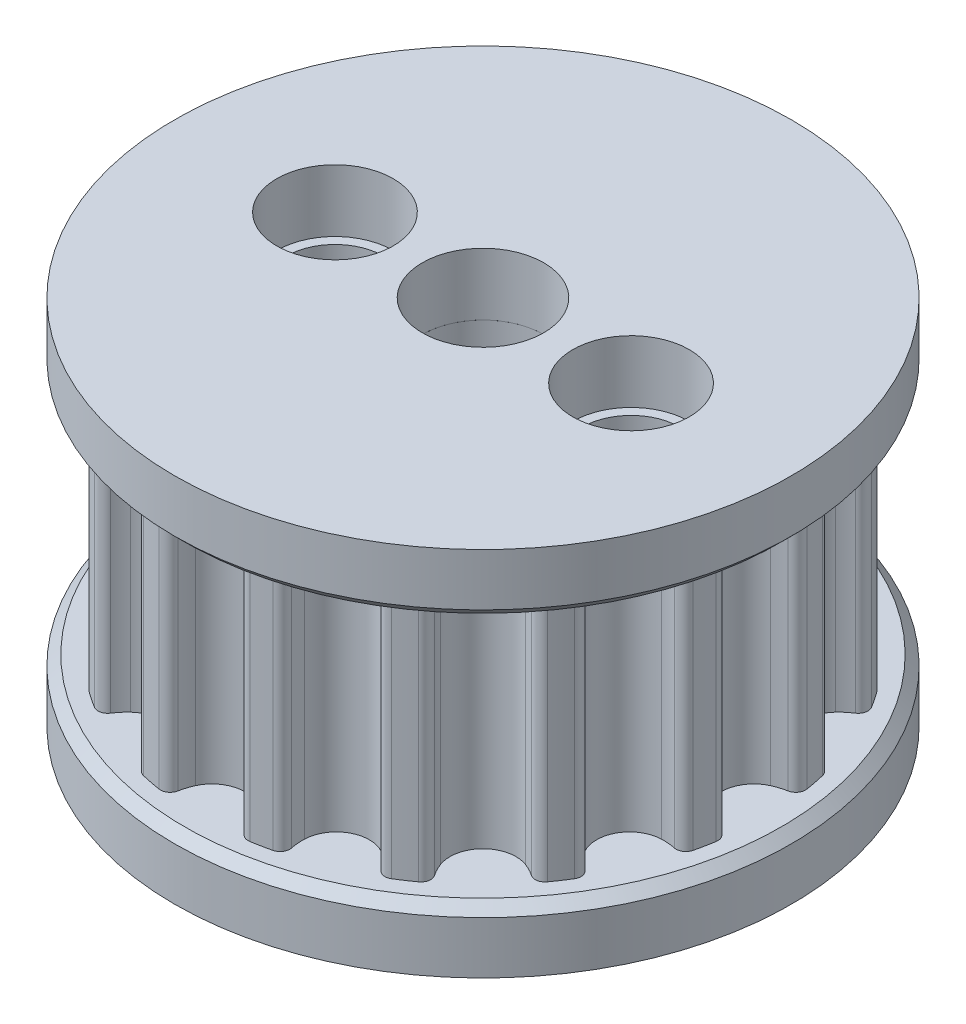
SolidWorks part; units mm, degrees
material "Alum Plate"
ref_plane "Front Plane" through (0, 0, 0) normal (0, 0, 1) x (1, 0, 0)
ref_plane "Top Plane" through (0, 0, 0) normal (0, 1, 0) x (1, 0, 0)
ref_plane "Right Plane" through (0, 0, 0) normal (1, 0, 0) x (0, 0, -1)
other "Bounding Box"
ref_plane "Default Plane" through (-8.9266, -12.7485, 0) normal (-0.1736, 0.9848, 0) x (0.9848, 0.1736, 0)
sketch "Sketch1" plane through (0, 0, 0) normal (0, 1, 0) x (1, 0, 0)
  line L0 (0, -7.8245) -> (0, 0) construction
  circle A0 centre (0, 0) radius 1.5625
  arc B0 (-1.8508, -6.777) -> (-1.6633, -7.0715) centre (-1.6061, -6.8282) ccw
  arc B1 (-1.6633, -7.0715) -> (-1.1695, -7.1697) centre (0, 0) ccw
  arc B2 (-1.1695, -7.1697) -> (-0.8836, -6.9694) centre (-1.1292, -6.923) ccw
  arc B3 (-0.7739, -6.6229) -> (-0.8836, -6.9694) centre (0.61, -7.2516) ccw
  arc B4 (0.7739, -6.6229) -> (-0.7739, -6.6229) centre (0, -6.9745) ccw
  arc B5 (0.8836, -6.9694) -> (0.7739, -6.6229) centre (-0.61, -7.2516) ccw
  arc B6 (0.8836, -6.9694) -> (1.1695, -7.1697) centre (1.1292, -6.923) ccw
  arc B7 (1.1695, -7.1697) -> (1.6633, -7.0715) centre (0, 0) ccw
  arc B8 (1.6633, -7.0715) -> (1.8508, -6.777) centre (1.6061, -6.8282) ccw
  arc B9 (1.8195, -6.4149) -> (1.8508, -6.777) centre (3.3386, -6.4662) ccw
  arc B10 (3.2495, -5.8226) -> (1.8195, -6.4149) centre (2.669, -6.4436) ccw
  arc B11 (3.4834, -6.1008) -> (3.2495, -5.8226) centre (2.2115, -6.9331) ccw
  arc B12 (3.4834, -6.1008) -> (3.8242, -6.1764) centre (3.6926, -5.9639) ccw
  arc B13 (3.8242, -6.1764) -> (4.2428, -5.8967) centre (0, 0) ccw
  arc B14 (4.2428, -5.8967) -> (4.3033, -5.5529) centre (4.0968, -5.6938) ccw
  arc B15 (4.1359, -5.2303) -> (4.3033, -5.5529) centre (5.559, -4.6963) ccw
  arc B16 (5.2303, -4.1359) -> (4.1359, -5.2303) centre (4.9317, -4.9317) ccw
  arc B17 (5.5529, -4.3033) -> (5.2303, -4.1359) centre (4.6963, -5.559) ccw
  arc B18 (5.5529, -4.3033) -> (5.8967, -4.2428) centre (5.6938, -4.0968) ccw
  arc B19 (5.8967, -4.2428) -> (6.1764, -3.8242) centre (0, 0) ccw
  arc B20 (6.1764, -3.8242) -> (6.1008, -3.4834) centre (5.9639, -3.6926) ccw
  arc B21 (5.8226, -3.2495) -> (6.1008, -3.4834) centre (6.9331, -2.2115) ccw
  arc B22 (6.4149, -1.8195) -> (5.8226, -3.2495) centre (6.4436, -2.669) ccw
  arc B23 (6.777, -1.8508) -> (6.4149, -1.8195) centre (6.4662, -3.3386) ccw
  arc B24 (6.777, -1.8508) -> (7.0715, -1.6633) centre (6.8282, -1.6061) ccw
  arc B25 (7.0715, -1.6633) -> (7.1697, -1.1695) centre (0, 0) ccw
  arc B26 (7.1697, -1.1695) -> (6.9694, -0.8836) centre (6.923, -1.1292) ccw
  arc B27 (6.6229, -0.7739) -> (6.9694, -0.8836) centre (7.2516, 0.61) ccw
  arc B28 (6.6229, 0.7739) -> (6.6229, -0.7739) centre (6.9745, 0) ccw
  arc B29 (6.9694, 0.8836) -> (6.6229, 0.7739) centre (7.2516, -0.61) ccw
  arc B30 (6.9694, 0.8836) -> (7.1697, 1.1695) centre (6.923, 1.1292) ccw
  arc B31 (7.1697, 1.1695) -> (7.0715, 1.6633) centre (0, 0) ccw
  arc B32 (7.0715, 1.6633) -> (6.777, 1.8508) centre (6.8282, 1.6061) ccw
  arc B33 (6.4149, 1.8195) -> (6.777, 1.8508) centre (6.4662, 3.3386) ccw
  arc B34 (5.8226, 3.2495) -> (6.4149, 1.8195) centre (6.4436, 2.669) ccw
  arc B35 (6.1008, 3.4834) -> (5.8226, 3.2495) centre (6.9331, 2.2115) ccw
  arc B36 (6.1008, 3.4834) -> (6.1764, 3.8242) centre (5.9639, 3.6926) ccw
  arc B37 (6.1764, 3.8242) -> (5.8967, 4.2428) centre (0, 0) ccw
  arc B38 (5.8967, 4.2428) -> (5.5529, 4.3033) centre (5.6938, 4.0968) ccw
  arc B39 (5.2303, 4.1359) -> (5.5529, 4.3033) centre (4.6963, 5.559) ccw
  arc B40 (4.1359, 5.2303) -> (5.2303, 4.1359) centre (4.9317, 4.9317) ccw
  arc B41 (4.3033, 5.5529) -> (4.1359, 5.2303) centre (5.559, 4.6963) ccw
  arc B42 (4.3033, 5.5529) -> (4.2428, 5.8967) centre (4.0968, 5.6938) ccw
  arc B43 (4.2428, 5.8967) -> (3.8242, 6.1764) centre (0, 0) ccw
  arc B44 (3.8242, 6.1764) -> (3.4834, 6.1008) centre (3.6926, 5.9639) ccw
  arc B45 (3.2495, 5.8226) -> (3.4834, 6.1008) centre (2.2115, 6.9331) ccw
  arc B46 (1.8195, 6.4149) -> (3.2495, 5.8226) centre (2.669, 6.4436) ccw
  arc B47 (1.8508, 6.777) -> (1.8195, 6.4149) centre (3.3386, 6.4662) ccw
  arc B48 (1.8508, 6.777) -> (1.6633, 7.0715) centre (1.6061, 6.8282) ccw
  arc B49 (1.6633, 7.0715) -> (1.1695, 7.1697) centre (0, 0) ccw
  arc B50 (1.1695, 7.1697) -> (0.8836, 6.9694) centre (1.1292, 6.923) ccw
  arc B51 (0.7739, 6.6229) -> (0.8836, 6.9694) centre (-0.61, 7.2516) ccw
  arc B52 (-0.7739, 6.6229) -> (0.7739, 6.6229) centre (0, 6.9745) ccw
  arc B53 (-0.8836, 6.9694) -> (-0.7739, 6.6229) centre (0.61, 7.2516) ccw
  arc B54 (-0.8836, 6.9694) -> (-1.1695, 7.1697) centre (-1.1292, 6.923) ccw
  arc B55 (-1.1695, 7.1697) -> (-1.6633, 7.0715) centre (0, 0) ccw
  arc B56 (-1.6633, 7.0715) -> (-1.8508, 6.777) centre (-1.6061, 6.8282) ccw
  arc B57 (-1.8195, 6.4149) -> (-1.8508, 6.777) centre (-3.3386, 6.4662) ccw
  arc B58 (-3.2495, 5.8226) -> (-1.8195, 6.4149) centre (-2.669, 6.4436) ccw
  arc B59 (-3.4834, 6.1008) -> (-3.2495, 5.8226) centre (-2.2115, 6.9331) ccw
  arc B60 (-3.4834, 6.1008) -> (-3.8242, 6.1764) centre (-3.6926, 5.9639) ccw
  arc B61 (-3.8242, 6.1764) -> (-4.2428, 5.8967) centre (0, 0) ccw
  arc B62 (-4.2428, 5.8967) -> (-4.3033, 5.5529) centre (-4.0968, 5.6938) ccw
  arc B63 (-4.1359, 5.2303) -> (-4.3033, 5.5529) centre (-5.559, 4.6963) ccw
  arc B64 (-5.2303, 4.1359) -> (-4.1359, 5.2303) centre (-4.9317, 4.9317) ccw
  arc B65 (-5.5529, 4.3033) -> (-5.2303, 4.1359) centre (-4.6963, 5.559) ccw
  arc B66 (-5.5529, 4.3033) -> (-5.8967, 4.2428) centre (-5.6938, 4.0968) ccw
  arc B67 (-5.8967, 4.2428) -> (-6.1764, 3.8242) centre (0, 0) ccw
  arc B68 (-6.1764, 3.8242) -> (-6.1008, 3.4834) centre (-5.9639, 3.6926) ccw
  arc B69 (-5.8226, 3.2495) -> (-6.1008, 3.4834) centre (-6.9331, 2.2115) ccw
  arc B70 (-6.4149, 1.8195) -> (-5.8226, 3.2495) centre (-6.4436, 2.669) ccw
  arc B71 (-6.777, 1.8508) -> (-6.4149, 1.8195) centre (-6.4662, 3.3386) ccw
  arc B72 (-6.777, 1.8508) -> (-7.0715, 1.6633) centre (-6.8282, 1.6061) ccw
  arc B73 (-7.0715, 1.6633) -> (-7.1697, 1.1695) centre (0, 0) ccw
  arc B74 (-7.1697, 1.1695) -> (-6.9694, 0.8836) centre (-6.923, 1.1292) ccw
  arc B75 (-6.6229, 0.7739) -> (-6.9694, 0.8836) centre (-7.2516, -0.61) ccw
  arc B76 (-6.6229, -0.7739) -> (-6.6229, 0.7739) centre (-6.9745, 0) ccw
  arc B77 (-6.9694, -0.8836) -> (-6.6229, -0.7739) centre (-7.2516, 0.61) ccw
  arc B78 (-6.9694, -0.8836) -> (-7.1697, -1.1695) centre (-6.923, -1.1292) ccw
  arc B79 (-7.1697, -1.1695) -> (-7.0715, -1.6633) centre (0, 0) ccw
  arc B80 (-7.0715, -1.6633) -> (-6.777, -1.8508) centre (-6.8282, -1.6061) ccw
  arc B81 (-6.4149, -1.8195) -> (-6.777, -1.8508) centre (-6.4662, -3.3386) ccw
  arc B82 (-5.8226, -3.2495) -> (-6.4149, -1.8195) centre (-6.4436, -2.669) ccw
  arc B83 (-6.1008, -3.4834) -> (-5.8226, -3.2495) centre (-6.9331, -2.2115) ccw
  arc B84 (-6.1008, -3.4834) -> (-6.1764, -3.8242) centre (-5.9639, -3.6926) ccw
  arc B85 (-6.1764, -3.8242) -> (-5.8967, -4.2428) centre (0, 0) ccw
  arc B86 (-5.8967, -4.2428) -> (-5.5529, -4.3033) centre (-5.6938, -4.0968) ccw
  arc B87 (-5.2303, -4.1359) -> (-5.5529, -4.3033) centre (-4.6963, -5.559) ccw
  arc B88 (-4.1359, -5.2303) -> (-5.2303, -4.1359) centre (-4.9317, -4.9317) ccw
  arc B89 (-4.3033, -5.5529) -> (-4.1359, -5.2303) centre (-5.559, -4.6963) ccw
  arc B90 (-4.3033, -5.5529) -> (-4.2428, -5.8967) centre (-4.0968, -5.6938) ccw
  arc B91 (-4.2428, -5.8967) -> (-3.8242, -6.1764) centre (0, 0) ccw
  arc B92 (-3.8242, -6.1764) -> (-3.4834, -6.1008) centre (-3.6926, -5.9639) ccw
  arc B93 (-3.2495, -5.8226) -> (-3.4834, -6.1008) centre (-2.2115, -6.9331) ccw
  arc B94 (-1.8195, -6.4149) -> (-3.2495, -5.8226) centre (-2.669, -6.4436) ccw
  arc B95 (-1.8508, -6.777) -> (-1.8195, -6.4149) centre (-3.3386, -6.4662) ccw
  dimension "D1" = 3.125
sketch_block_instance "Block-GT2 16 Tooth Profile-1"
sketch_block "Block-GT2 16 Tooth Profile" parameters "D1"=2.1152
extrude "Boss-Extrude1" add sketch "Sketch1" along normal mid plane 6.35
sketch "Sketch2" plane through (0, -3.175, 0) normal (0, -1, 0) x (1, 0, 0)
  circle A0 centre (0, 0) radius 7.9375
  circle A1 centre (0, 0) radius 1.5625 construction
  circle A2 centre (0, 0) radius 1.5625
  dimension "D1" = 15.875
extrude "Boss-Extrude2" add sketch "Sketch2" along normal blind 1.6002 separate body
sketch "Sketch3" plane through (0, -4.7752, 0) normal (0, -1, 0) x (1, 0, 0)
  line L0 (0, 0) -> (3.81, 0) construction
  line L1 (0, 0) -> (-3.81, 0) construction
  circle A0 centre (-3.81, 0) radius 1.5
  circle A1 centre (3.81, 0) radius 1.5
  dimension "D1" = 3
  dimension "D2" = 3.81
extrude "Cut-Extrude1" cut sketch "Sketch3" against normal through all
sketch "Sketch4" plane through (0, -3.175, 0) normal (0, -1, 0) x (1, 0, 0)
  circle A0 centre (-3.81, 0) radius 1.25
  circle A1 centre (3.81, 0) radius 1.25
  dimension "D1" = 2.5
extrude "Cut-Extrude2" cut sketch "Sketch4" against normal through all
chamfer "Chamfer1" distance 0.254 angle 45 1 edges at (0, -3.175, -7.9375)
mirror "Mirror2" about plane through (0, 0, 0) normal (0, 1, 0) of bodies 107 105
